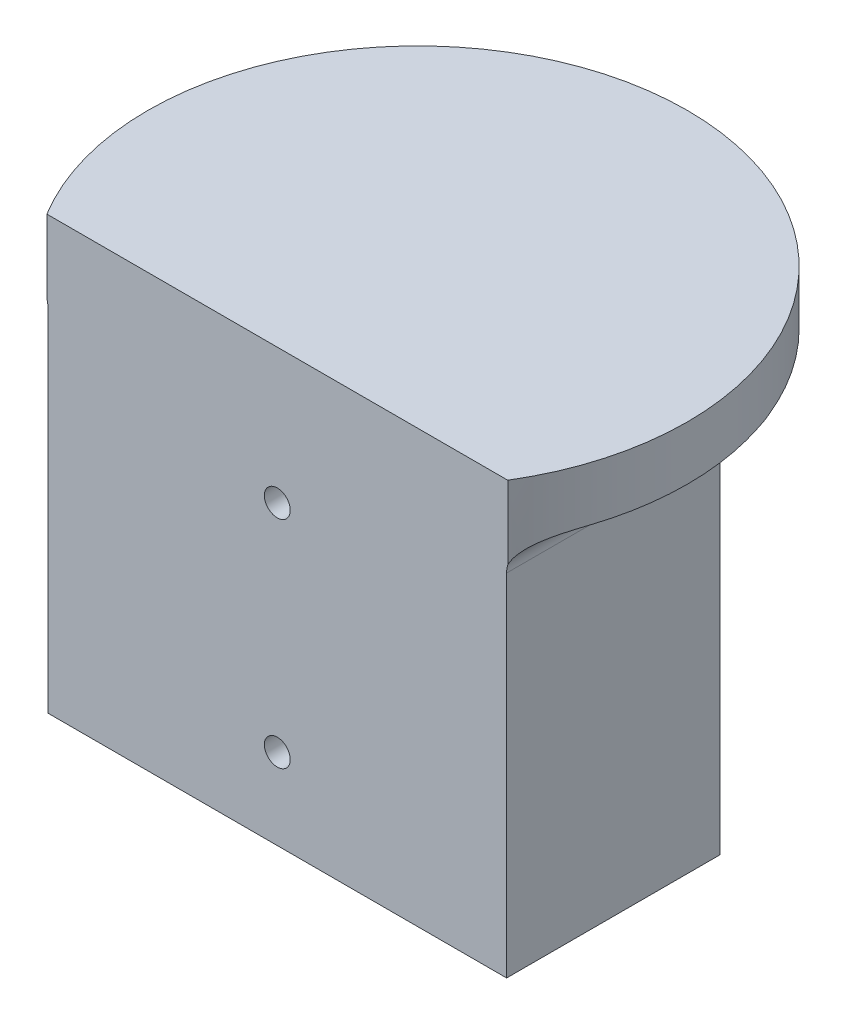
SolidWorks part; units mm, degrees
ref_plane "Front Plane" through (0, 0, 0) normal (0, 0, 1) x (1, 0, 0)
ref_plane "Top Plane" through (0, 0, 0) normal (0, 1, 0) x (1, 0, 0)
ref_plane "Right Plane" through (0, 0, 0) normal (1, 0, 0) x (0, 0, -1)
sketch "Sketch1" plane through (0, 0, 0) normal (0, 1, 0) x (1, 0, 0)
  line L0 (-37.5, -8.5) -> (37.5, -8.5) construction
  line L1 (-37.5, -8.5) -> (-37.5, 8.5) construction
  line L2 (-37.5, 8.5) -> (37.5, 8.5) construction
  line L3 (37.5, -8.5) -> (37.5, 8.5) construction
  line L4 (-37.5, -8.5) -> (37.5, 8.5) construction
  line L5 (-37.5, 8.5) -> (37.5, -8.5) construction
  line L6 (-42.5, 13.5) -> (-32.5, 13.5)
  line L7 (-42.5, 13.5) -> (-42.5, -16)
  line L8 (-42.5, -16) -> (-32.5, -16)
  line L9 (-32.5, 13.5) -> (-32.5, -16)
  line L10 (32.5, 13.5) -> (42.5, 13.5)
  line L11 (32.5, 13.5) -> (32.5, -16)
  line L12 (32.5, -16) -> (42.5, -16)
  line L13 (42.5, 13.5) -> (42.5, -16)
  line L14 (-42.5, -16) -> (42.5, -16)
  line L15 (-42.5, -16) -> (-42.5, -26)
  line L16 (-42.5, -26) -> (42.5, -26)
  line L17 (42.5, -16) -> (42.5, -26)
  circle A0 centre (-37.5, 8.5) radius 2.75
  circle A1 centre (37.5, 8.5) radius 2.75
  circle A2 centre (-37.5, -8.5) radius 2.75
  circle A3 centre (37.5, -8.5) radius 2.75
  point P8 (0, 0)
  point P19 (-37.5, 13.5)
  point P20 (37.5, 13.5)
  point P22 (0, 0)
  dimension "D1" = 5.5
  dimension "D2" = 75
  dimension "D3" = 17
  dimension "D4" = 10
  dimension "D5" = 5
  dimension "D6" = 7.5
  dimension "D7" = 10
extrude "Boss-Extrude1" add sketch "Sketch1" along normal blind 10 contours L9 L6 L7 L8 A2 A0 | L17 L12 L14 L8 L15 L16 | L13 L10 L11 L12 A3 A1 region at (-37.5, 0, 1.49) region at (0, 0, 21) region at (37.5, 0, 1.49)
sketch "Sketch6" plane through (0, 10, 0) normal (0, 1, 0) x (1, 0, 0)
  line L8 (-32.5, -16) -> (-32.5, 13.5)
  line L9 (-32.5, 13.5) -> (-42.5, 13.5)
  line L10 (-42.5, 13.5) -> (-42.5, -26)
  line L11 (-42.5, -26) -> (42.5, -26)
  line L12 (42.5, -26) -> (42.5, 13.5)
  line L13 (42.5, 13.5) -> (32.5, 13.5)
  line L14 (32.5, 13.5) -> (32.5, -16)
  line L15 (32.5, -16) -> (-32.5, -16)
  line L16 (-32.5, -16) -> (-32.5, 13.5)
  line L17 (-32.5, 13.5) -> (-42.5, 13.5)
  line L18 (-42.5, 13.5) -> (-42.5, -26)
  line L19 (-42.5, -26) -> (42.5, -26)
  line L20 (42.5, -26) -> (42.5, 13.5)
  line L21 (42.5, 13.5) -> (32.5, 13.5)
  line L22 (32.5, 13.5) -> (32.5, -16)
  line L23 (32.5, -16) -> (-32.5, -16)
  dimension "D1" = 0
extrude "Boss-Extrude4" add sketch "Sketch6" along normal blind 60
sketch "Sketch7" plane through (0, 70, 0) normal (0, 1, 0) x (1, 0, 0)
  line L0 (-42.5, -26) -> (42.5, -26) construction
  line L1 (-42.5, -26) -> (42.5, -26)
  line L2 (42.5, -26) -> (42.7083, -26)
  line L3 (-42.5, -26) -> (-42.7083, -26)
  arc A0 (42.7083, -26) -> (-42.7083, -26) centre (0, 0) ccw
  dimension "D1" = 100
extrude "Boss-Extrude5" add sketch "Sketch7" along normal blind 10
fillet "Fillet2" radius 5 7 edges at (42.5, 70, 6.25) (37.5, 70, -13.5) (32.5, 70, 1.25) (0, 70, 16) (-32.5, 70, 1.25) (-37.5, 70, -13.5) (-42.5, 70, 6.25)
sketch "Sketch8" plane through (0, 0, 16) normal (0, 0, -1) x (-1, 0, 0)
  line L0 (32.5, 0) -> (-32.5, 0) construction
  circle A0 centre (0, 55) radius 5.4767
  circle A1 centre (0, 15) radius 5.4767
  point P0 (0, 55)
  point P2 (0, 15)
  dimension "D1" = 40
  dimension "D2" = 15
hole_wizard "CBORE for M4 SHCS2" positions "Sketch8" profile "Sketch9" counterbore size "M4" standard "ANSI Metric" end condition through all
sketch "Sketch9" plane through (0, 55, 16) normal (1, 0, 0) x (0, 1, 0)
  line L0 (0, 0) -> (0, 10)
  line L1 (0, 10) -> (2.4, 10)
  line L3 (2.4, 10) -> (2.4, 4)
  line L4 (2.4, 4) -> (4, 4)
  line L5 (4, 4) -> (4, 0)
  line L7 (4, 0) -> (0, 0)
  line L11 (0, -6.35) -> (0, 107.95) construction
  dimension "Thru Hole Dia." = 4.8
  dimension "Thru Hole Depth" = 10
  dimension "C'Bore Dia." = 8
  dimension "C'Bore Depth" = 4
